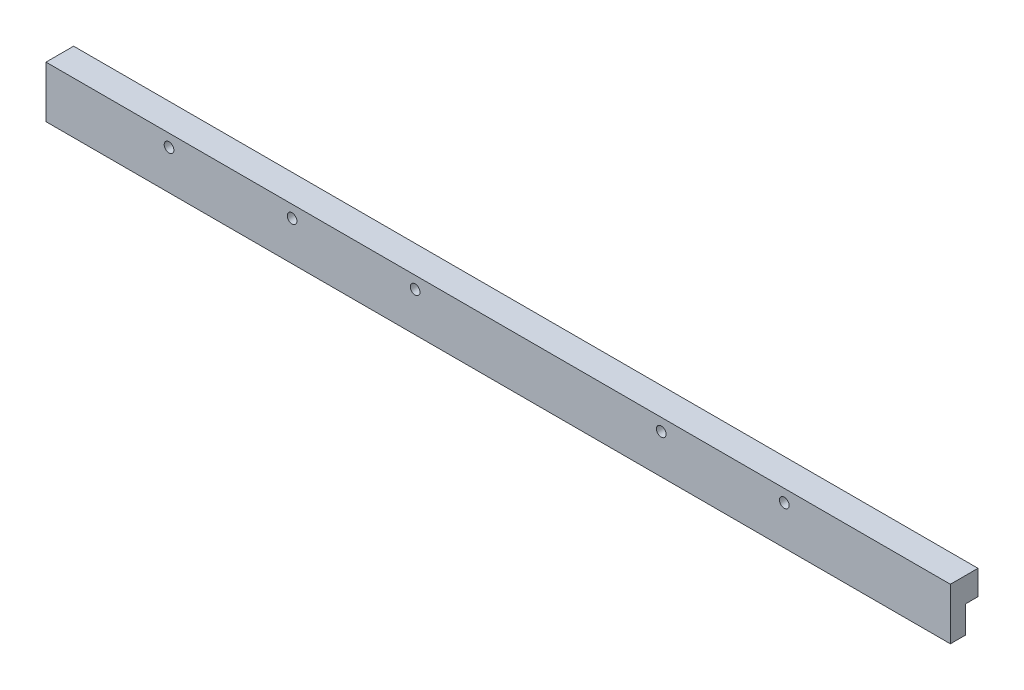
SolidWorks part; units mm, degrees
note: The reader was unsure of these and kept them because the rebuilt part matched: shared geometry of "Sketch2<3>".
ref_plane "Front Plane" through (0, 0, 0) normal (0, 0, 1) x (1, 0, 0)
ref_plane "Top Plane" through (0, 0, 0) normal (0, 1, 0) x (1, 0, 0)
ref_plane "Right Plane" through (0, 0, 0) normal (1, 0, 0) x (0, 0, -1)
sketch "Sketch1" plane through (0, 0, 0) normal (0, 0, 1) x (1, 0, 0)
  line L0 (6.5929, 7.3704) -> (176.701, 203.0574)
  line L1 (6.5929, 7.3704) -> (176.701, 7.3704)
  line L2 (176.701, 203.0574) -> (292.6093, 77.8877)
  line L3 (176.701, 203.0574) -> (176.701, 7.3704)
  line L4 (6.5929, 7.3704) -> (4.0986, 9.5386)
  line L6 (4.0986, 9.5386) -> (174.2067, 205.2256)
  line L10 (174.2067, 205.2256) -> (176.701, 203.0574)
  line L11 (292.6093, 77.8877) -> (294.8662, 79.9776)
  line L12 (294.8662, 79.9776) -> (176.701, 207.5845)
  line L13 (176.701, 203.0574) -> (176.701, 207.5845)
  line L14 (176.701, 207.5845) -> (174.2067, 205.2256)
  line L15 (4.0986, 9.5386) -> (6.5929, 7.3704)
  line L16 (6.5929, 7.3704) -> (9.3301, 4.6332)
  line L17 (9.3301, 4.6332) -> (179.222, 200.3349)
  line L18 (292.6093, 77.8877) -> (289.803, 75.306)
  line L19 (289.803, 75.306) -> (176.701, 197.4308)
  dimension "D1" = 42.8
  dimension "D3" = 90
  dimension "D4" = 90
  dimension "D5" = 41
extrude "Boss-Extrude1" add sketch "Sketch1" along normal blind 177.8 contours L10 L6 L4 L0 | L13 L14 L10 | L13 L2 L11 L12 | L1 L17 L3 L0 | L19 L18 L2 L17 | L3 L17 L2
ref_plane "Plane1" through (0, 0, 0) normal (0, 0, -1) x (-1, 0, 0)
sketch "Sketch2" plane through (0, 0, 0) normal (0, 0, -1) x (-1, 0, 0)
  line L4 (-294.8662, 79.9776) -> (-176.701, 207.5845) construction
  line L5 (-176.701, 207.5845) -> (-294.8662, 79.9776)
  line L6 (-176.701, 207.5845) -> (-4.0362, 9.4669)
  line L11 (-294.8662, 308.5776) -> (-4.0362, 308.5776)
  line L12 (-4.0362, 308.5776) -> (-4.0362, 9.4669)
  line L14 (-294.8662, 308.5776) -> (-294.8662, 79.9776)
  line L15 (-4.0986, 9.5386) -> (-174.2067, 205.2256) construction
  circle A6 centre (-109.5518, 215.6074) radius 6.35
  circle A7 centre (-50.0992, 143.6384) radius 6.35
  circle A8 centre (0, 64.0701) radius 6.35
  dimension "D4" = 94.0268
  dimension "D1" = 228.6
  dimension "D2" = 93.3497
  dimension "D3" = 290.83
extrude "Boss-Extrude2" add sketch "Sketch2" against normal blind 3.175
ref_plane "Plane2" through (0, 0, 177.8) normal (0, 0, 1) x (1, 0, 0)
ref_plane "Plane3" through (0, 0, 88.9) normal (0, 0, 1) x (1, 0, 0)
mirror "Mirror1" about plane through (0, 0, 88.9) normal (0, 0, 1) of "Boss-Extrude2"
sketch "Sketch3" plane through (-2.3884, 2.0762, 0) normal (-0.7547, 0.6561, 0) x (0.6561, 0.7547, 0)
  line L0 (0, -88.9) -> (269.1756, -88.9) construction
  line L1 (-55, -88.9) -> (55, -88.9) construction
  line L2 (269.1756, -174.625) -> (269.1756, -3.175) construction
  line L3 (9.8879, -115.3039) -> (147.0479, -115.3039)
  line L4 (147.0479, -115.3039) -> (146.9349, 0)
  line L5 (235.5345, 0) -> (9.7927, 0) construction
  line L6 (146.9349, 0) -> (210.4349, 0)
  line L7 (272.5923, 0) -> (9.7927, 0) construction
  line L8 (210.4349, 0) -> (210.4349, -115.3039)
  line L9 (210.4349, -115.3039) -> (147.0479, -115.3039)
  line L10 (147.0479, -115.3039) -> (210.4349, -115.3039)
  line L11 (9.8879, -174.625) -> (9.8879, -3.175) construction
  dimension "D1" = 63.5
  dimension "D3" = 137.16
extrude "Cut-Extrude1" cut sketch "Sketch3" against normal blind 7.62
sketch "Sketch4" plane through (0, 0, 3.175) normal (0, 0, 1) x (1, 0, 0)
  line L0 (176.701, 207.5845) -> (4.0362, 9.4669) construction
  circle A0 centre (115.1385, 136.947) radius 35.56
extrude "Cut-Extrude2" cut sketch "Sketch4" against normal blind 5.08
sketch "Sketch5" plane through (0, 0, 0) normal (0, 0, -1) x (-1, 0, 0)
  line L0 (-4.0362, 308.5776) -> (-4.0362, 9.4669) construction
  line L1 (-4.0362, 87.8093) -> (23.7187, 87.8093)
  line L2 (-4.0362, 87.8093) -> (-4.0362, 41.2582)
  line L3 (-4.0362, 41.2582) -> (23.7187, 41.2582)
  line L4 (23.7187, 87.8093) -> (23.7187, 41.2582)
  circle A0 centre (0, 64.0701) radius 6.35
  line M4 (-4.0362, 9.4669) -> (-4.0362, 308.5776)
extrude "Boss-Extrude3" add sketch "Sketch5" against normal blind 3.175 contours L4 L1 L3 A0 M4
sketch "Sketch6" plane through (0, 0, 177.8) normal (0, 0, 1) x (1, 0, 0)
  line L1 (4.0362, 87.8093) -> (-23.7187, 87.8093)
  line L2 (4.0362, 87.8093) -> (4.0362, 41.2582)
  line L3 (4.0362, 41.2582) -> (-23.7187, 41.2582)
  line L4 (-23.7187, 87.8093) -> (-23.7187, 41.2582)
  circle A0 centre (0, 64.0701) radius 6.35
  line M6 (4.0362, 308.5776) -> (4.0362, 9.4669)
extrude "Boss-Extrude4" add sketch "Sketch6" against normal blind 3.175 contours L1 L4 L3 A0 M6
extrude "Cut-Extrude3" cut sketch "Sketch2<3>" against normal blind 203.2 contours A8
sketch "Sketch2<3>" plane through (0, 0, 0) normal (0, 0, -1) x (-1, 0, 0) same geometry as "Sketch2"
sketch "Sketch7" plane through (198.615, 183.9195, 0) normal (0.7337, 0.6794, 0) x (0, 0, -1)
  line L0 (-174.625, -141.6623) -> (-3.175, -141.6623) construction
  line L1 (-3.175, -141.6623) -> (-88.9, -141.6623) construction
  line L2 (-88.9, -141.6623) -> (-88.9, -123.8823) construction
  line L3 (-88.9, 55) -> (-88.9, -55) construction
  line L4 (-88.9, -123.8823) -> (-36.6474, -123.8823) construction
  line L5 (-36.6474, -123.8823) -> (-36.6474, -141.6623) construction
  line L6 (-36.6474, -141.6623) -> (-140.9512, -141.6623) construction
  line L7 (-140.9512, -141.6623) -> (-140.9512, -123.8823) construction
  line L8 (-140.9512, -123.8823) -> (-88.9, -123.8823) construction
  line L10 (-140.9512, -123.8823) -> (-36.6474, -123.8823)
  line L11 (-140.9512, -123.8823) -> (-140.9512, -141.6623)
  line L12 (-140.9512, -141.6623) -> (-36.6474, -141.6623)
  line L13 (-36.6474, -123.8823) -> (-36.6474, -141.6623)
  dimension "D1" = 17.78
extrude "Cut-Extrude4" cut sketch "Sketch7" against normal blind 7.62
sketch "Sketch8" plane through (0, 0, 0) normal (0, 0, -1) x (-1, 0, 0)
  line L0 (-294.8662, 79.9776) -> (-294.8662, 191.7376) construction
  line L1 (-294.8662, 308.5776) -> (-294.8662, 79.9776) construction
sketch "Sketch9" plane through (294.8662, 0, 0) normal (1, 0, 0) x (0, 0, -1)
  line L1 (0, 186.7117) -> (5.0949, 186.7117)
  line L2 (0, 186.7117) -> (0, 196.8717)
  line L3 (0, 196.8717) -> (5.0949, 196.8717)
  line L4 (5.0949, 186.7117) -> (5.0949, 196.8717)
  line L5 (0, 308.5776) -> (0, 79.9776) construction
  line L6 (5.0949, 196.8717) -> (11.4058, 196.8717)
  line L7 (5.0949, 196.8717) -> (5.0949, 175.5607)
  line L8 (5.0949, 175.5607) -> (11.4058, 175.5607)
  line L9 (11.4058, 196.8717) -> (11.4058, 175.5607)
  line M1 (0, 79.9776) -> (0, 308.5776)
  dimension "D1" = 10.16
extrude "Boss-Extrude5" add sketch "Sketch9" against normal blind 373.38 contours L1 L4 L3 M1 | L9 L6 L4 L7 L8
ref_plane "Plane4" through (0, 0, 88.9) normal (0, 0, 1) x (1, 0, 0)
mirror "Mirror2" about plane through (0, 0, 88.9) normal (0, 0, 1) of "Boss-Extrude5"
sketch "Sketch10" plane through (294.8662, 0, 0) normal (1, 0, 0) x (0, 0, -1)
  line L0 (0, 308.5776) -> (0, 79.9776) construction
  line L1 (0, 205.7357) -> (16.3899, 205.7357)
  line L2 (0, 205.7357) -> (0, 149.8827)
  line L3 (0, 149.8827) -> (16.3899, 149.8827)
  line L4 (16.3899, 205.7357) -> (16.3899, 149.8827)
extrude "Cut-Extrude5" cut sketch "Sketch10" against normal blind 50.8
sketch "Sketch11" plane through (0, 0, 0) normal (0, 0, -1) x (-1, 0, 0)
  line L0 (-294.8662, 308.5776) -> (-294.8662, 79.9776) construction
  line L1 (-294.8662, 209.1619) -> (-257.555, 209.1619)
  line L2 (-294.8662, 209.1619) -> (-294.8662, 139.1254)
  line L3 (-294.8662, 139.1254) -> (-257.555, 139.1254)
  line L4 (-257.555, 209.1619) -> (-257.555, 139.1254)
extrude "Cut-Extrude6" cut sketch "Sketch11" against normal blind 63.5
sketch "Sketch12" plane through (198.615, 183.9195, 0) normal (0.7337, 0.6794, 0) x (0, 0, -1)
  line L0 (-171.533, 28.0226) -> (-143.202, -115.1621)
  line L1 (-33.4545, -115.1621) -> (-6.2281, 28.0226)
extrude "Cut-Extrude-Thin3" cut sketch "Sketch12" against normal blind 1.27 thin thin type one direction reverse wall 3.302
sketch "Sketch13" plane through (198.615, 183.9195, 0) normal (0.7337, 0.6794, 0) x (0, 0, -1)
  line L0 (-171.533, 28.0226) -> (-171.3752, 27.2252)
  line L1 (-171.3752, 27.2252) -> (-168.2938, 28.6635)
  line L2 (-168.2938, 28.6635) -> (-171.533, 28.0226)
  line L3 (-168.2938, 28.6635) -> (-139.9628, -114.5212) construction
  line L4 (-143.202, -115.1621) -> (-140.1206, -113.7238)
  line L5 (-140.1206, -113.7238) -> (-139.9628, -114.5212)
  line L6 (-143.202, -115.1621) -> (-139.9628, -114.5212)
  line L7 (-171.533, 28.0226) -> (-143.202, -115.1621) construction
  line L8 (-171.533, 28.0226) -> (-143.202, -115.1621) construction
  line L9 (-9.4719, 28.6394) -> (-6.3826, 27.2098)
  line L10 (-33.4545, -115.1621) -> (-6.2281, 28.0226) construction
  line L11 (-6.3826, 27.2098) -> (-6.2281, 28.0226)
  line L12 (-6.2281, 28.0226) -> (-9.4719, 28.6394)
  line L13 (-36.6984, -114.5453) -> (-33.3027, -114.3636)
  line L14 (-33.4545, -115.1621) -> (-6.2281, 28.0226) construction
  line L15 (-33.3027, -114.3636) -> (-33.4545, -115.1621)
  line L16 (-33.4545, -115.1621) -> (-36.6984, -114.5453)
  dimension "D1" = 0.8128
  dimension "D2" = 0.8128
  dimension "D3" = 0.8128
  dimension "D4" = 0.8128
extrude "Boss-Extrude6" add sketch "Sketch13" against normal blind 1.27 separate body
sketch "Sketch14" plane through (0, 0, 3.175) normal (0, 0, 1) x (1, 0, 0)
  line L0 (4.0362, 308.5776) -> (4.0362, 9.4669) construction
  circle A0 centre (25.6262, 167.7264) radius 6.35
  dimension "D1" = 21.59
extrude "Cut-Extrude7" cut sketch "Sketch14" against normal blind 6.35
sketch "Sketch15" plane through (0, 0, 177.8) normal (0, 0, 1) x (1, 0, 0)
  circle A0 centre (25.6262, 167.7264) radius 6.35
extrude "Cut-Extrude8" cut sketch "Sketch15" against normal blind 6.35
sketch "Sketch16" plane through (0, 0, -11.4058) normal (0, 0, -1) x (-1, 0, 0)
  line L0 (-244.0662, 191.7917) -> (-4.0362, 191.7917) construction
  line L1 (-244.0662, 196.8717) -> (-244.0662, 186.7117) construction
  line L2 (-4.0362, 308.5776) -> (-4.0362, 9.4669) construction
  line L3 (78.5138, 196.8717) -> (78.5138, 175.5607) construction
  circle A0 centre (-175.4862, 191.7917) radius 2
  circle A2 centre (-73.8862, 191.7917) radius 2
  circle A3 centre (-23.0862, 191.7917) radius 2
  circle A4 centre (27.7138, 191.7917) radius 2
  dimension "D1" = 50.8
  dimension "D2" = 101.6
  dimension "D4" = 50.8
  dimension "D5" = 50.8
extrude "Cut-Extrude9" cut sketch "Sketch16" against normal blind 203.2
sketch "Sketch17" plane through (0, 0, 189.2058) normal (0, 0, 1) x (1, 0, 0)
  line L0 (175.4862, 191.7917) -> (294.8662, 191.7376) construction
  circle A0 centre (226.2862, 191.7376) radius 2
  dimension "D1" = 50.8
extrude "Cut-Extrude10" cut sketch "Sketch17" against normal blind 50.8
sketch "Sketch18" plane through (198.615, 183.9195, 0) normal (0.7337, 0.6794, 0) x (0, 0, -1)
  line L0 (-170.825, -33.5095) -> (-170.825, -115.9129)
  line L1 (-170.825, -115.9129) -> (-148.0215, -115.9129)
  line L2 (-148.0215, -115.9129) -> (-165.1241, -33.5095)
  line L3 (-165.1241, -33.5095) -> (-170.825, -33.5095)
extrude "Cut-Extrude11" cut sketch "Sketch18" against normal blind 50.8
sketch "Sketch19" plane through (198.615, 183.9195, 0) normal (0.7337, 0.6794, 0) x (0, 0, -1)
  line L0 (-27.791, -115.9129) -> (-12.8356, -35.3555)
  line L1 (-12.8356, -35.3555) -> (-7.2062, -35.3555)
  line L2 (-7.2062, -35.3555) -> (-7.2062, -115.9129)
  line L3 (-7.2062, -115.9129) -> (-27.791, -115.9129)
extrude "Cut-Extrude12" cut sketch "Sketch19" against normal blind 135.636
sketch "Sketch20" plane through (0, 0, 177.8) normal (0, 0, 1) x (1, 0, 0)
  line L0 (294.8662, 308.5776) -> (4.0362, 308.5776) construction
  line L1 (162.8579, 292.5756) -> (264.4579, 292.5756)
  line L2 (162.8579, 292.5756) -> (162.8579, 241.7756)
  line L3 (162.8579, 241.7756) -> (264.4579, 241.7756)
  line L4 (264.4579, 292.5756) -> (264.4579, 241.7756)
  line L5 (169.2079, 292.4947) -> (258.1079, 292.4947)
  line L6 (169.2079, 292.4947) -> (169.2079, 273.4447)
  line L7 (169.2079, 273.4447) -> (258.1079, 273.4447)
  line L8 (258.1079, 292.4947) -> (258.1079, 273.4447)
  circle A0 centre (162.8579, 241.7756) radius 1.55
  circle A1 centre (162.8579, 292.5756) radius 1.55
  circle A2 centre (264.4579, 292.5756) radius 1.55
  circle A3 centre (264.4579, 241.7756) radius 1.55
  dimension "D3" = 16.002
  dimension "D1" = 101.6
  dimension "D2" = 50.8
  dimension "D4" = 6.35
  dimension "D5" = 88.9
  dimension "D6" = 19.05
extrude "Cut-Extrude13" cut sketch "Sketch20" against normal blind 25.4 contours L2 A1 L1 | L1 A1 L2 | L4 A2 L1 | L1 A2 L4 | L2 A0 L3 | L3 A0 L2 | L4 A3 L3 | L3 A3 L4 | L8 L5 L6 L7
sketch "Sketch22" plane through (0, 0, 0) normal (0, 0, -1) x (-1, 0, 0)
  line L0 (-294.8662, 308.5776) -> (-4.0362, 308.5776) construction
  line L1 (-264.5816, 292.5756) -> (-162.9816, 292.5756)
  line L2 (-264.5816, 292.5756) -> (-264.5816, 241.7756)
  line L3 (-264.5816, 241.7756) -> (-162.9816, 241.7756)
  line L4 (-162.9816, 292.5756) -> (-162.9816, 241.7756)
  line L5 (-258.2316, 292.5534) -> (-169.3316, 292.5534)
  line L6 (-258.2316, 292.5534) -> (-258.2316, 273.5034)
  line L7 (-258.2316, 273.5034) -> (-169.3316, 273.5034)
  line L8 (-169.3316, 292.5534) -> (-169.3316, 273.5034)
  circle A0 centre (-264.5816, 292.5756) radius 1.55
  circle A1 centre (-264.5816, 241.7756) radius 1.55
  circle A2 centre (-162.9816, 292.5756) radius 1.55
  circle A3 centre (-162.9816, 241.7756) radius 1.55
  dimension "D3" = 16.002
  dimension "D1" = 101.6
  dimension "D2" = 50.8
  dimension "D4" = 6.35
  dimension "D5" = 88.9
  dimension "D6" = 19.05
extrude "Cut-Extrude14" cut sketch "Sketch22" against normal blind 25.4 contours L1 A0 L2 | L2 A0 L1 | L2 A1 L3 | L3 A1 L2 | L4 A2 L1 | L1 A2 L4 | L4 A3 L3 | L3 A3 L4 | L8 L5 L6 L7
sketch "Sketch23" plane through (0, 0, 0) normal (0, 0, -1) x (-1, 0, 0)
  line L0 (-292.2866, 77.5908) -> (-174.4076, 204.953) construction
  line L1 (-292.6093, 77.8877) -> (-289.803, 75.306) construction
  line L2 (-176.701, 207.5845) -> (-4.0362, 9.4669) construction
  line L3 (-7.2586, 7.3704) -> (-177.0204, 202.13)
  line L4 (-6.5929, 7.3704) -> (-11.7063, 7.3704) construction
  circle A0 centre (-282.4885, 88.1771) radius 1.5
  circle A1 centre (-262.696, 109.5619) radius 1.5
  circle A2 centre (-243.4899, 130.3131) radius 1.5
  circle A3 centre (-222.238, 153.2747) radius 1.5
  circle A4 centre (-17.5669, 19.1965) radius 1.5
  circle A5 centre (-33.1684, 37.0955) radius 1.5
  circle A6 centre (-50.887, 57.4232) radius 1.5
  circle A7 centre (-147.3861, 168.1319) radius 1.5
  circle A8 centre (-72.1847, 81.857) radius 1.5
extrude "Cut-Extrude15" cut sketch "Sketch23" against normal blind 12.7 contours A0 L0 | L0 A0 | A1 L0 | L0 A1 | A2 L0 | L0 A2 | A3 L0 | L0 A3 | L3 A7 | L3 A7 | L3 A6 | L3 A6 | L3 A5 | L3 A5 | L3 A4 | L3 A4
sketch "Sketch24" plane through (0, 0, 177.8) normal (0, 0, 1) x (1, 0, 0)
  line L0 (7.3883, 7.3704) -> (179.0187, 205.0816) construction
  line L1 (6.5929, 7.3704) -> (11.7063, 7.3704) construction
  line L2 (176.701, 207.5845) -> (294.8662, 79.9776) construction
  line L3 (292.1599, 77.4743) -> (174.5457, 205.1115) construction
  line L4 (176.701, 207.5845) -> (4.0362, 9.4669) construction
  line L5 (292.6093, 77.8877) -> (289.803, 75.306) construction
  circle A0 centre (277.2218, 93.6853) radius 1.5
  circle A1 centre (256.088, 116.6201) radius 1.5
  circle A2 centre (233.3528, 141.2929) radius 1.5
  circle A3 centre (211.7585, 164.7274) radius 1.5
  circle A4 centre (135.0206, 154.3977) radius 1.5
  circle A5 centre (113.6721, 129.805) radius 1.5
  circle A6 centre (89.5465, 102.0133) radius 1.5
  circle A7 centre (62.6765, 71.0602) radius 1.5
  circle A8 centre (39.5224, 44.3875) radius 1.5
extrude "Cut-Extrude16" cut sketch "Sketch24" against normal blind 12.7
sketch "Sketch25" plane through (294.8662, 0, 0) normal (1, 0, 0) x (0, 0, -1)
  line L0 (-177.8, 61.4383) -> (-177.8, -61.4383) construction
  line L1 (-177.8, 308.5776) -> (84.5319, 308.5776)
  line L2 (-177.8, 308.5776) -> (-177.8, -40.6331)
  line L3 (-177.8, -40.6331) -> (84.5319, -40.6331)
  line L4 (84.5319, 308.5776) -> (84.5319, -40.6331)
  line L5 (-174.625, 308.5776) -> (-177.8, 308.5776) construction
extrude "Cut-Extrude17" cut sketch "Sketch25" against normal blind 381
ref_plane "Plane5" through (108.1762, 0, 0) normal (1, 0, 0) x (0, 0, -1)
sketch "Sketch26" plane through (108.1762, 0, 0) normal (1, 0, 0) x (0, 0, -1)
  line L1 (-189.2058, 196.8717) -> (-177.5333, 196.8717)
  line L2 (-189.2058, 196.8717) -> (-189.2058, 175.336)
  line L3 (-189.2058, 175.336) -> (-177.5333, 175.336)
  line L4 (-177.5333, 196.8717) -> (-177.5333, 175.336)
